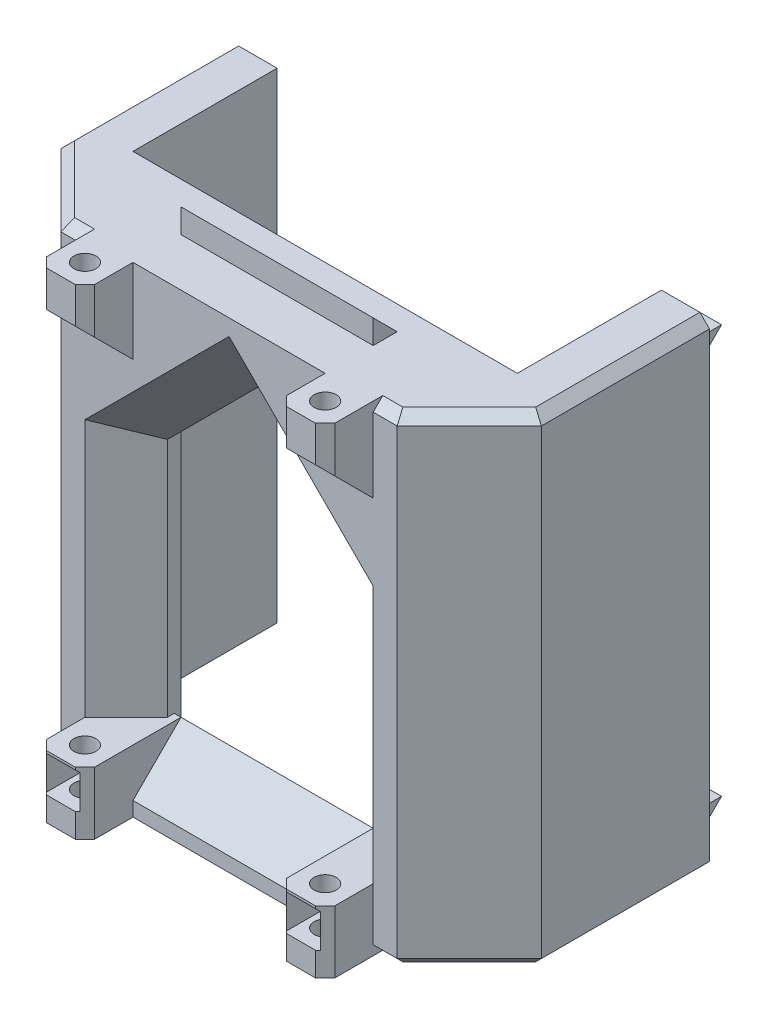
SolidWorks part; units mm, degrees
ref_plane "Front Plane" through (0, 0, 0) normal (0, 0, 1) x (1, 0, 0)
ref_plane "Top Plane" through (0, 0, 0) normal (0, 1, 0) x (1, 0, 0)
ref_plane "Right Plane" through (0, 0, 0) normal (1, 0, 0) x (0, 0, -1)
sketch "Sketch1" plane through (0, 0, 0) normal (0, 1, 0) x (1, 0, 0)
  line L0 (-50, 0) -> (50, 0)
  line L1 (-50, 0) -> (-50, 50)
  line L2 (50, 0) -> (50, 50)
  line L3 (-50, 50) -> (50, 50)
  point P4 (0, 0)
extrude "Boss-Extrude1" add sketch "Sketch1" along normal blind 100
chamfer "Chamfer1" distance 15 2 edges at (-50, 50, 0) (50, 50, 0)
ref_plane "Plane1" through (0, 100, 0) normal (0, 1, 0) x (1, 0, 0)
sketch "Sketch2" plane through (0, 100, 0) normal (0, 1, 0) x (1, 0, 0)
  line L0 (0, 0) -> (0, 20) construction
  line L1 (-40, 20) -> (40, 20)
  line L2 (-40, 20) -> (-50, 20) construction
  line L4 (-50, 50) -> (-50, 15) construction
  line L5 (40, 20) -> (50, 20) construction
  line L6 (50, 15) -> (50, 50) construction
  line L7 (-40, 20) -> (-40, 50)
  line L8 (50, 50) -> (-50, 50) construction
  line L9 (40, 20) -> (40, 50)
  line L10 (40, 50) -> (-40, 50)
  point P6 (0, 20)
  dimension "D1" = 20
  dimension "D2" = 10
extrude "Cut-Extrude1" cut sketch "Sketch2" against normal up to next
sketch "Sketch3" plane through (0, 100, 0) normal (0, 1, 0) x (1, 0, 0)
  line L0 (-20, 0) -> (20, 0) construction
  line L1 (-35, 0) -> (35, 0) construction
  line L2 (20, 0) -> (20, -10)
  line L3 (20, -10) -> (30, -10)
  line L4 (30, -10) -> (30, 0)
  line L5 (30, 0) -> (20, 0)
  line L6 (-20, 0) -> (-20, -10)
  line L7 (-20, -10) -> (-30, -10)
  line L8 (-30, -10) -> (-30, 0)
  line L9 (-30, 0) -> (-20, 0)
  circle A0 centre (-25, -5) radius 2.3
  circle A1 centre (25, -5) radius 2.3
  point P6 (0, 0)
  dimension "D5" = 4.6
  dimension "D6" = 4.6
  dimension "D1" = 10
  dimension "D2" = 10
  dimension "D3" = 40
  dimension "D4" = 10
extrude "Boss-Extrude2" add sketch "Sketch3" against normal blind 7.5
extrude "Boss-Extrude3" add sketch "Sketch3<2>" along normal blind 13 from surface starting at face at (0, 0, -27)
sketch "Sketch3<2>" plane through (0, 100, 0) normal (0, 1, 0) x (1, 0, 0) same geometry as "Sketch3"
ref_plane "Plane2" through (0, 0, 10) normal (0, 0, 1) x (1, 0, 0)
sketch "Sketch4" plane through (0, 0, 10) normal (0, 0, 1) x (1, 0, 0)
  line L0 (25, 0) -> (25, 5) construction
  line L1 (30, 0) -> (20, 0) construction
  line L2 (21.5, 5) -> (28.5, 5)
  line L3 (28.5, 5) -> (28.5, 8.5)
  line L4 (28.5, 8.5) -> (21.5, 8.5)
  line L5 (21.5, 8.5) -> (21.5, 5)
  line L6 (-25, 0) -> (-25, 5) construction
  line L7 (-20, 0) -> (-30, 0) construction
  line L8 (-28.5, 5) -> (-21.5, 5)
  line L9 (-21.5, 5) -> (-21.5, 8.5)
  line L10 (-21.5, 8.5) -> (-28.5, 8.5)
  line L11 (-28.5, 8.5) -> (-28.5, 5)
  point P7 (25, 5)
  point P16 (-25, 5)
  dimension "D1" = 5
  dimension "D2" = 7
  dimension "D3" = 3.5
  dimension "D4" = 7
extrude "Cut-Extrude2" cut sketch "Sketch4" against normal blind 9
chamfer "Chamfer2" distance 4 2 edges at (25, 8.5, 10) (-25, 8.5, 10)
chamfer "Chamfer3" distance 10 2 edges at (25, 92.5, 0) (-25, 92.5, 0)
sketch "Sketch5" plane through (0, 100, 0) normal (0, 1, 0) x (1, 0, 0)
  circle A0 centre (-25, -5) radius 3.55
  circle A1 centre (25, -5) radius 3.55
  dimension "D1" = 7.1
  dimension "D2" = 7.1
extrude "Cut-Extrude3" cut sketch "Sketch5" against normal up to next from offset 7 offset against normal yes
sketch "Sketch6" plane through (0, 100, 0) normal (0, 1, 0) x (1, 0, 0)
  line L0 (-20, 0) -> (-20, 10) construction
  line L1 (-20, 10) -> (20, 10)
  line L2 (20, 10) -> (20, 15)
  line L3 (20, 15) -> (-20, 15)
  line L4 (-20, 15) -> (-20, 10)
  dimension "D1" = 10
  dimension "D2" = 40
  dimension "D3" = 5
extrude "Boss-Extrude4" add sketch "Sketch6" along normal blind 5
chamfer "Chamfer4" distance 5 1 edges at (0, 105, -15)
extrude "Cut-Extrude4" cut sketch "Sketch6<2>" along normal blind 5 from surface starting at face at (0, 0, -12.7778)
sketch "Sketch6<2>" plane through (0, 100, 0) normal (0, 1, 0) x (1, 0, 0) same geometry as "Sketch6"
chamfer "Chamfer5" distance 4.75 1 edges at (0, 5, -15)
ref_plane "Plane3" through (0, 0, -50) normal (0, 0, -1) x (-1, 0, 0)
sketch "Sketch7" plane through (0, 0, -50) normal (0, 0, -1) x (-1, 0, 0)
  line L0 (45, 0) -> (45, 5) construction
  line L1 (40, 0) -> (50, 0) construction
  line L2 (45, 100) -> (45, 95) construction
  line L3 (40, 100) -> (50, 100) construction
  line L4 (47.5, 5) -> (42.5, 5)
  line L5 (42.5, 5) -> (42.5, 10)
  line L6 (42.5, 10) -> (47.5, 10)
  line L7 (47.5, 10) -> (47.5, 5)
  line L8 (47.5, 95) -> (42.5, 95)
  line L9 (42.5, 95) -> (42.5, 90)
  line L10 (42.5, 90) -> (47.5, 90)
  line L11 (47.5, 90) -> (47.5, 95)
  point P11 (45, 5)
  point P16 (45, 95)
  dimension "D2" = 5
  dimension "D4" = 5
  dimension "D1" = 5
  dimension "D3" = 5
  dimension "D5" = 5
  dimension "D6" = 5
extrude "Cut-Extrude5" cut sketch "Sketch7" against normal blind 5
sketch "Sketch8" plane through (0, 0, -50) normal (0, 0, -1) x (-1, 0, 0)
  line L0 (-45, 100) -> (-45, 95) construction
  line L1 (-50, 100) -> (-40, 100) construction
  line L2 (-45, 0) -> (-45, 5) construction
  line L3 (-50, 0) -> (-40, 0) construction
  line L4 (-47.5, 95) -> (-42.5, 95)
  line L5 (-42.5, 95) -> (-42.5, 90)
  line L6 (-42.5, 90) -> (-47.5, 90)
  line L7 (-47.5, 90) -> (-47.5, 95)
  line L8 (-47.5, 5) -> (-42.5, 5)
  line L9 (-42.5, 5) -> (-42.5, 10)
  line L10 (-42.5, 10) -> (-47.5, 10)
  line L11 (-47.5, 10) -> (-47.5, 5)
  point P11 (-45, 95)
  point P16 (-45, 5)
  dimension "D3" = 5
  dimension "D4" = 5
  dimension "D1" = 5
  dimension "D2" = 5
  dimension "D5" = 5
  dimension "D6" = 5
extrude "Boss-Extrude5" add sketch "Sketch8" along normal blind 5
chamfer "Chamfer6" distance 5 2 edges at (45, 5, -55) (45, 90, -55)
chamfer "Chamfer7" distance 4.75 2 edges at (-45, 90, -45) (-45, 5, -45)
chamfer "Chamfer8" distance 2 8 edges at (30, 6.5, 10) (20, 6.5, 10) (-30, 6.5, 10) (-20, 6.5, 10) (-30, 96.25, 10) (-20, 96.25, 10) (20, 96.25, 10) (30, 96.25, 10)
sketch "Sketch9" plane through (0, 0, 10) normal (0, 0, 1) x (1, 0, 0)
  line L0 (-20, 82.5) -> (20, 82.5) construction
  line L1 (-20, 13) -> (20, 13) construction
  line L2 (-20, 82.5) -> (-20, 13) construction
  line L3 (20, 82.5) -> (20, 13) construction
  line L4 (0, 82.5) -> (-20, 62.5)
  line L5 (0, 82.5) -> (20, 62.5)
  line L6 (20, 62.5) -> (20, 13)
  line L7 (20, 13) -> (-20, 13)
  line L8 (-20, 13) -> (-20, 62.5)
extrude "Cut-Extrude6" cut sketch "Sketch9" against normal up to next from surface starting at face at (0, 49.1, 0)
chamfer "Chamfer9" distance 10 9 edges at (20, 37.75, 0) (10, 72.5, 0) (-10, 72.5, 0) (-20, 37.75, 0) (0, 13, -20) (-20, 37.75, -20) (-10, 72.5, -20) (10, 72.5, -20) (20, 37.75, -20)
chamfer "Chamfer10" distance 10 1 edges at (0, 13, 0)
chamfer "Chamfer11" distance 2 4 edges at (20, 37.75, -10) (-20, 37.75, -10) (-10, 72.5, -10) (10, 72.5, -10)
chamfer "Chamfer12" distance 2 12 edges at (50, 0, -32.5) (42.5, 0, -7.5) (32.5, 0, 0) (-50, 0, -32.5) (-42.5, 0, -7.5) (-32.5, 0, 0) (-50, 100, -32.5) (-42.5, 100, -7.5) (-32.5, 100, 0) (50, 100, -32.5) (32.5, 100, 0) (42.5, 100, -7.5)
